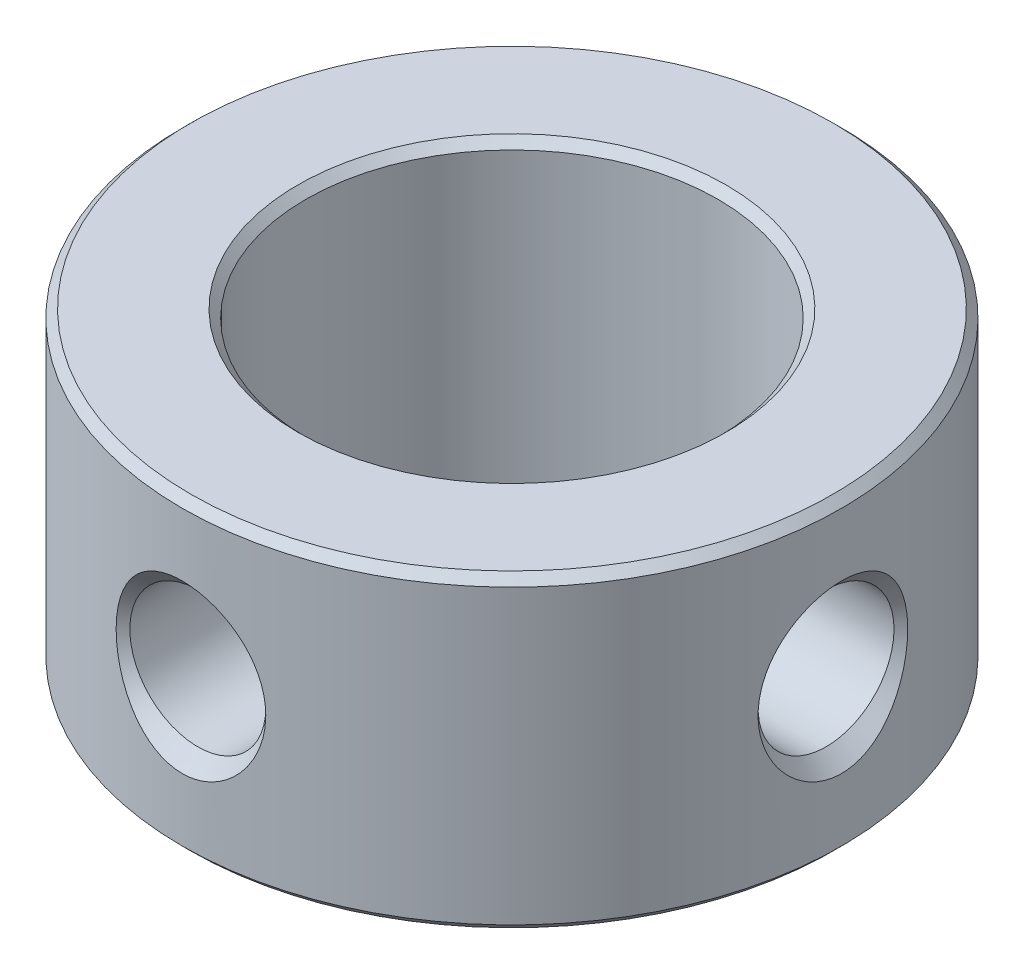
SolidWorks part; units mm, degrees
material "6061-T6 (SS)"
ref_plane "Front Plane" through (0, 0, 0) normal (0, 0, 1) x (1, 0, 0)
ref_plane "Top Plane" through (0, 0, 0) normal (0, 1, 0) x (1, 0, 0)
ref_plane "Right Plane" through (0, 0, 0) normal (1, 0, 0) x (0, 0, -1)
sketch "ProfileS" plane through (0, 0, 0) normal (0, 1, 0) x (1, 0, 0)
  circle A0 centre (0, 0) radius 5
  circle A1 centre (0, 0) radius 8
  dimension "InnerDia" = 10
  dimension "RefOuterDia" = 16
  dimension "DiaControl" = 3
extrude "Profile" add sketch "ProfileS" along normal mid plane 7.5
ref_plane "SetScrewPlane" through (0, 0, 8) normal (0, 0, 1) x (1, 0, 0)
hole_wizard " Tapped Hole1" positions "Sketch1" profile "Sketch2" tap size "M4x0.7" standard "ANSI Metric" end condition up to next
sketch "Sketch1" plane through (0, 0, 8) normal (0, 0, 1) x (1, 0, 0)
  point P0 (0, 0)
sketch "Sketch2" plane through (0, 0, 8) normal (1, 0, 0) x (0, -1, 0)
  line L0 (0, 0) -> (0, 16)
  line L1 (0, 16) -> (1.65, 16)
  line L2 (1.65, 16) -> (1.65, 0.375)
  line L3 (1.65, 0.375) -> (2.025, 0)
  line L5 (2.025, 0) -> (0, 0)
  line L6 (-1.65, 0.375) -> (-2.025, 0) construction
  line L11 (0, -6.35) -> (0, 107.95) construction
  dimension "Thru Tap Drill Dia." = 3.3
  dimension "Thru Tap Drill Depth" = 16
  dimension "Near C'Sink Dia." = 4.05
  dimension "Near C'Sink Angle" = 90
cosmetic thread "Hole Thread1" parameters "D2"=4
pattern_circular "CirPattern1" count 2 every 90 about axis through (0, 3.75, 0) along (0, -1, 0) of " Tapped Hole1" reverse direction yes
chamfer "OuterC" distance 0.2 angle 45 2 edges at (0, 3.75, 8) (0, -3.75, 8)
chamfer "InnerC" distance 0.2 angle 45 2 edges at (0, 3.75, 5) (0, -3.75, 5)
